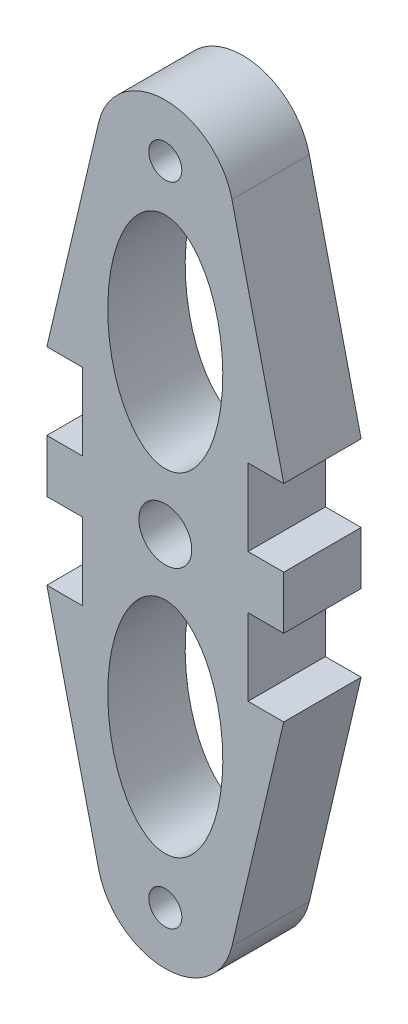
SolidWorks part; units mm, degrees
material "Acrylic (Medium-high impact)"
ref_plane "Front Plane" through (0, 0, 0) normal (0, 0, 1) x (1, 0, 0)
ref_plane "Top Plane" through (0, 0, 0) normal (0, 1, 0) x (1, 0, 0)
ref_plane "Right Plane" through (0, 0, 0) normal (1, 0, 0) x (0, 0, -1)
sketch "Sketch1" plane through (0, 0, 0) normal (0, 0, 1) x (1, 0, 0)
  line L0 (-213.0435, 465.4024) -> (49786.9565, 465.4024) construction
  line L1 (781.4092, 465.4024) -> (778.7092, 465.4024)
  line L2 (781.4092, 465.4024) -> (781.4092, 471.2024)
  line L3 (781.4092, 471.2024) -> (778.7092, 471.2024)
  line L4 (787.6592, -515.9255) -> (787.6592, 49484.0745) construction
  line L5 (-215.2235, 463.4024) -> (49784.7765, 463.4024) construction
  line L6 (793.9092, 471.2024) -> (793.9092, 487.8374) construction
  line L7 (-217.5077, 461.4024) -> (49782.4923, 461.4024) construction
  line L8 (785.6592, -537.0976) -> (785.6592, 49462.9024) construction
  line L9 (789.6592, -536.5976) -> (789.6592, 49463.4024) construction
  line L10 (793.9092, 465.4024) -> (796.6092, 465.4024)
  line L11 (781.4092, 471.2024) -> (793.9092, 471.2024) construction
  line L12 (793.9092, 471.2024) -> (796.6092, 471.2024)
  line L13 (793.9092, 465.4024) -> (793.9092, 471.2024)
  line L14 (778.7092, 465.4024) -> (778.7092, 461.4024)
  line L15 (796.6092, 465.4024) -> (796.6092, 461.4024)
  line L16 (786.4092, 487.8374) -> (782.6227, 487.8374) construction
  line L17 (781.4092, 461.4024) -> (778.7092, 461.4024)
  line L18 (793.9092, 471.2024) -> (793.1879, 471.1692) construction
  line L19 (781.4092, 455.6024) -> (778.7092, 455.6024)
  line L20 (781.4092, 461.4024) -> (781.4092, 455.6024)
  line L21 (793.9092, 461.4024) -> (796.6092, 461.4024)
  line L22 (793.9092, 461.4024) -> (793.9092, 455.6024)
  line L23 (793.9092, 455.6024) -> (796.6092, 455.6024)
  line L24 (778.7092, 471.2024) -> (782.6227, 487.8374)
  line L25 (792.6956, 487.8374) -> (796.6092, 471.2024)
  line L26 (792.6956, 438.9674) -> (796.6092, 455.6024)
  line L27 (788.9092, 438.9674) -> (792.6956, 438.9674) construction
  line L28 (786.4092, 438.9674) -> (782.6227, 438.9674) construction
  line L29 (778.7092, 455.6024) -> (782.6227, 438.9674)
  line L35 (788.9092, 487.8374) -> (792.6956, 487.8374) construction
  arc A0 (782.6227, 487.8374) -> (792.6956, 487.8374) centre (787.6592, 486.6525) cw
  arc A1 (782.6227, 438.9674) -> (792.6956, 438.9674) centre (787.6592, 440.1522) ccw
  circle A3 centre (787.6592, 487.8374) radius 1.25
  circle A5 centre (787.6592, 438.9674) radius 1.25
  circle A6 centre (787.6592, 463.4024) radius 2
  ellipse E0 centre (787.6592, 475.9981) end of major axis (787.6592, 484.3002) minor radius 4.3465
  ellipse E1 centre (787.6592, 450.8066) end of major axis (787.6592, 442.5045) minor radius 4.3465
  point P10 (778.7092, 463.4024)
  point P19 (796.6092, 463.4024)
  dimension "D1" = 4
  dimension "D3" = 5.8
  dimension "D10" = 5.174
  dimension "D2" = 2.7
  dimension "D4" = 24.435
  dimension "D5" = 12.5
  dimension "D6" = 16.6042
  dimension "D7" = 8.693
  dimension "D8" = 2.2937
extrude "Boss-Extrude1" add sketch "Sketch1" along normal blind 5.85 contours L3 A3 A5 region at (782.0052, 468.3024, 0)
